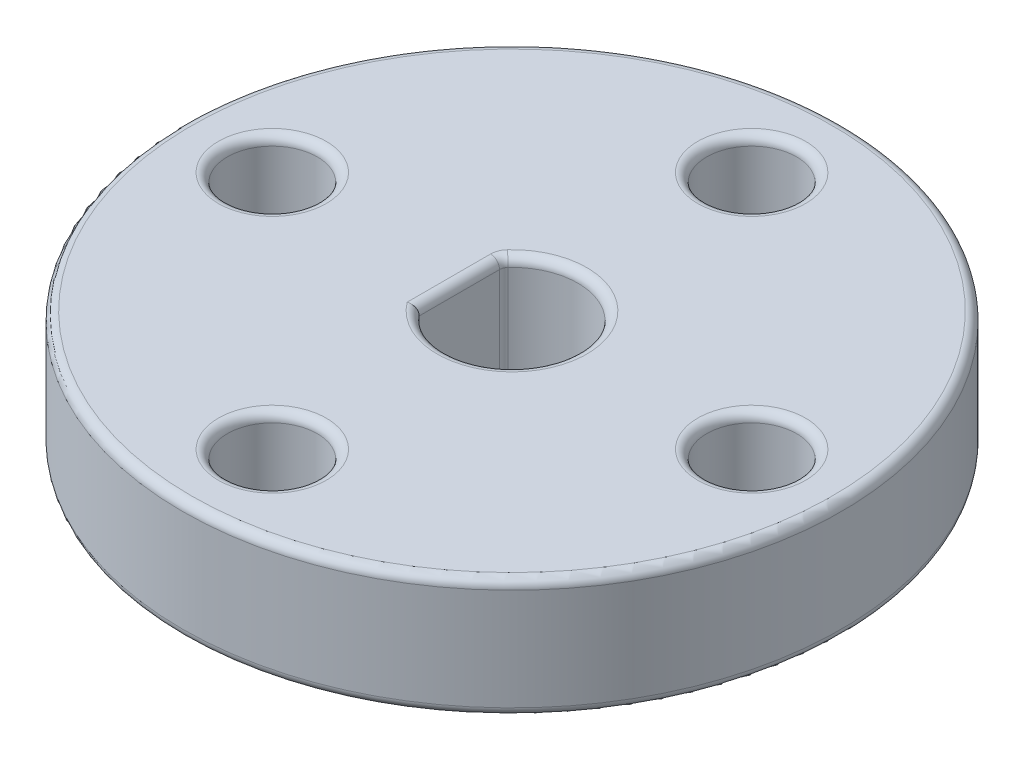
SolidWorks part; units mm, degrees
ref_plane "Front Plane" through (0, 0, 0) normal (0, 0, 1) x (1, 0, 0)
ref_plane "Top Plane" through (0, 0, 0) normal (0, 1, 0) x (1, 0, 0)
ref_plane "Right Plane" through (0, 0, 0) normal (1, 0, 0) x (0, 0, -1)
sketch "Sketch1" plane through (0, 0, 0) normal (0, 1, 0) x (1, 0, 0)
  line L0 (3, 47.4052) -> (0, 54.5)
  line L1 (0, 54.5) -> (-3, 47.4052)
  line L2 (0, 54.5) -> (0, 47.5) construction
  line L3 (-3, 47.4052) -> (0, 47.5) construction
  line L4 (0, 47.5) -> (3, 47.4052) construction
  line L5 (-3, 47.4052) -> (0, 47.5) construction
  line L6 (0, 47.5) -> (3, 47.4052) construction
  line L7 (13.8515, 45.4355) -> (12.5686, 53.0309)
  line L8 (12.5686, 53.0309) -> (8.0132, 46.8192)
  line L9 (23.9563, 41.0164) -> (24.4596, 48.703)
  line L10 (24.4596, 48.703) -> (18.5945, 43.7092)
  line L11 (32.7696, 34.3861) -> (35.0319, 41.7494)
  line L12 (35.0319, 41.7494) -> (28.1733, 38.2428)
  line L13 (39.8163, 25.902) -> (43.7157, 32.5451)
  line L14 (43.7157, 32.5451) -> (36.2333, 30.7148)
  line L15 (44.7164, 16.0216) -> (50.0428, 21.5863)
  line L16 (50.0428, 21.5863) -> (42.3399, 21.5309)
  line L17 (47.2059, 5.2774) -> (53.672, 9.4638)
  line L18 (53.672, 9.4638) -> (46.164, 11.1862)
  line L19 (47.1505, -5.7513) -> (54.4078, -3.1689)
  line L20 (54.4078, -3.1689) -> (47.4994, 0.2386)
  line L21 (44.5532, -16.4699) -> (52.2104, -15.6308)
  line L22 (52.2104, -15.6308) -> (46.2741, -10.722)
  line L23 (39.5541, -26.3007) -> (47.1984, -27.25)
  line L24 (47.1984, -27.25) -> (42.5541, -21.1045)
  line L25 (32.4225, -34.7135) -> (39.6419, -37.4002)
  line L26 (39.6419, -37.4002) -> (36.54, -30.3493)
  line L27 (23.5431, -41.255) -> (29.9482, -45.5341)
  line L28 (29.9482, -45.5341) -> (28.556, -37.9579)
  line L29 (13.3944, -45.5723) -> (18.6401, -51.2132)
  line L30 (18.6401, -51.2132) -> (19.0326, -43.5202)
  line L31 (2.5237, -47.4329) -> (6.3271, -54.1315)
  line L32 (6.3271, -54.1315) -> (8.4831, -46.7364)
  line L33 (-8.4831, -46.7364) -> (-6.3271, -54.1315)
  line L34 (-6.3271, -54.1315) -> (-2.5237, -47.4329)
  line L35 (-19.0326, -43.5202) -> (-18.6401, -51.2132)
  line L36 (-18.6401, -51.2132) -> (-13.3944, -45.5723)
  line L37 (-28.556, -37.9579) -> (-29.9482, -45.5341)
  line L38 (-29.9482, -45.5341) -> (-23.5431, -41.255)
  line L39 (-36.54, -30.3493) -> (-39.6419, -37.4002)
  line L40 (-39.6419, -37.4002) -> (-32.4225, -34.7135)
  line L41 (-42.5541, -21.1045) -> (-47.1984, -27.25)
  line L42 (-47.1984, -27.25) -> (-39.5541, -26.3007)
  line L43 (-46.2741, -10.722) -> (-52.2104, -15.6308)
  line L44 (-52.2104, -15.6308) -> (-44.5532, -16.4699)
  line L45 (-47.4994, 0.2386) -> (-54.4078, -3.1689)
  line L46 (-54.4078, -3.1689) -> (-47.1505, -5.7513)
  line L47 (-46.164, 11.1862) -> (-53.672, 9.4638)
  line L48 (-53.672, 9.4638) -> (-47.2059, 5.2774)
  line L49 (-42.3399, 21.5309) -> (-50.0428, 21.5863)
  line L50 (-50.0428, 21.5863) -> (-44.7164, 16.0216)
  line L51 (-36.2333, 30.7148) -> (-43.7157, 32.5451)
  line L52 (-43.7157, 32.5451) -> (-39.8163, 25.902)
  line L53 (-28.1733, 38.2428) -> (-35.0319, 41.7494)
  line L54 (-35.0319, 41.7494) -> (-32.7696, 34.3861)
  line L55 (-18.5945, 43.7092) -> (-24.4596, 48.703)
  line L56 (-24.4596, 48.703) -> (-23.9563, 41.0164)
  line L57 (-8.0132, 46.8192) -> (-12.5686, 53.0309)
  line L58 (-12.5686, 53.0309) -> (-13.8515, 45.4355)
  line L59 (0, 16) -> (0, 37.5) construction
  line L60 (-4.5, 37.229) -> (-4.5, 15.3542)
  line L61 (4.5, 37.229) -> (4.5, 15.3542)
  line L62 (37.229, -4.5) -> (15.3542, -4.5)
  line L63 (37.229, 4.5) -> (15.3542, 4.5)
  line L64 (-4.5, -37.229) -> (-4.5, -15.3542)
  line L65 (4.5, -37.229) -> (4.5, -15.3542)
  line L66 (-37.229, 4.5) -> (-15.3542, 4.5)
  line L67 (-37.229, -4.5) -> (-15.3542, -4.5)
  line L68 (0, 0) -> (0, 5.8384) construction
  line L69 (-1.7, 1.3964) -> (-1.7, -1.3964)
  line L70 (0, 0) -> (-4.8311, 0) construction
  line L71 (0, 0) -> (0, 5.8384) construction
  line L72 (0, 0) -> (-4.8311, 0) construction
  circle A0 centre (0, 0) radius 47.5
  circle A1 centre (0, 0) radius 37.5
  circle A2 centre (0, 0) radius 5
  circle A3 centre (0, 0) radius 2.2
  circle A4 centre (0, 0) radius 16
  circle A5 centre (0, 0) radius 46.5
  circle A6 centre (-8, 0) radius 1.5
  circle A7 centre (0, 8) radius 1.5
  circle A8 centre (8, 0) radius 1.5
  circle A9 centre (0, -8) radius 1.5
  circle A10 centre (-8, 0) radius 1.5
  circle A11 centre (0, 8) radius 1.5
  circle A12 centre (8, 0) radius 1.5
  circle A13 centre (0, -8) radius 1.5
  circle A15 centre (0, 0) radius 11
  point P88 (0, 0)
  point P111 (0, 0)
  point P123 (0, 0)
  point P135 (0, 0)
  dimension "D1" = 95
  dimension "D5" = 75
  dimension "D6" = 10
  dimension "D7" = 4.4
  dimension "D8" = 32
  dimension "D9" = 4
  dimension "D11" = 0.5
  dimension "D12" = 1
  dimension "D13" = 22
  dimension "D2" = 7
  dimension "D3" = 3
  dimension "D10" = 9
  dimension "D4" = 27
extrude "Boss-Extrude1" add sketch "Sketch1" along normal blind 4 contours A15 A2 A6 A7 A8 A9 | A2 A3 | L69 A3 region at (-1.9021, 0, 0) region at (-4.8586, 0, 0) region at (-10.6889, 0, 0)
fillet "Fillet1" radius 0.3 15 edges at (-1.7, 4, 0) (-8, 0, 1.5) (0, 0, -6.5) (8, 0, 1.5) (0, 0, 9.5) (0, 0, 11) (2.2, 0, 0) (-1.7, 0, 0) (-8, 4, 1.5) (0, 4, -6.5) (8, 4, 1.5) (0, 4, 9.5) (0, 4, 11) (2.2, 4, 0) (-1.7, 2, -1.3964)
